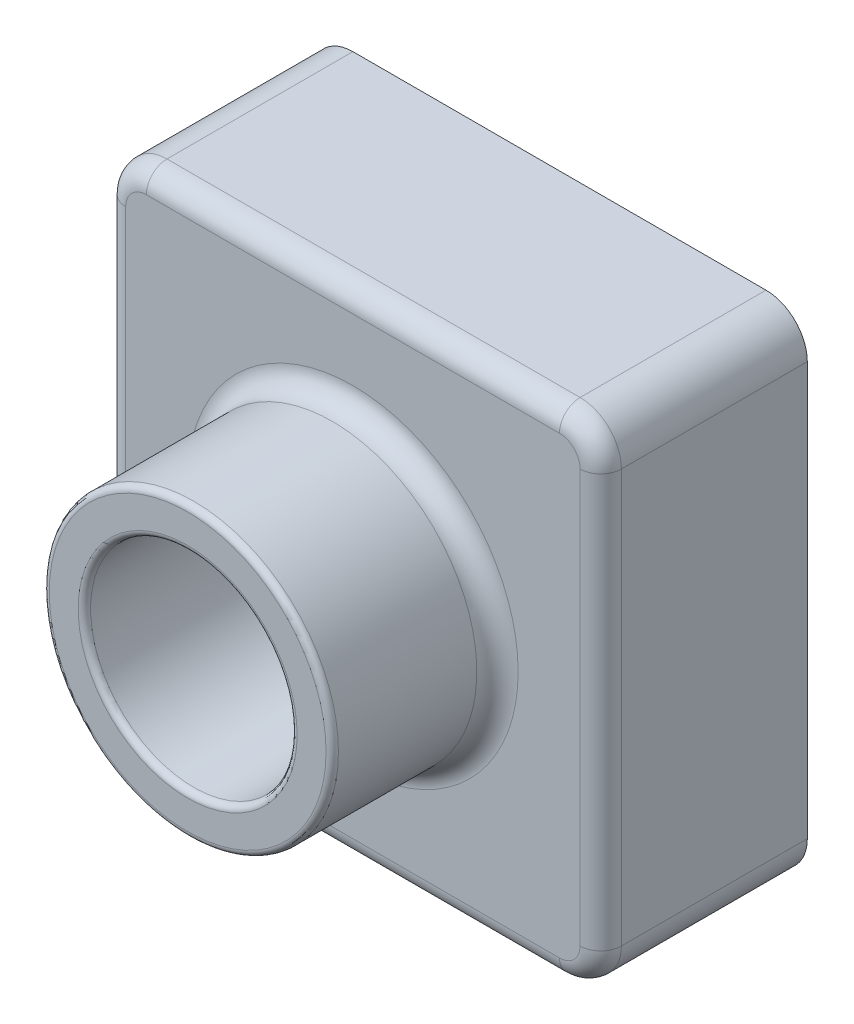
SolidWorks part; units mm, degrees
ref_plane "Front Plane" through (0, 0, 0) normal (0, 0, 1) x (1, 0, 0)
ref_plane "Top Plane" through (0, 0, 0) normal (0, 1, 0) x (1, 0, 0)
ref_plane "Right Plane" through (0, 0, 0) normal (1, 0, 0) x (0, 0, -1)
sketch "Sketch4" plane through (0, 0, 0) normal (0, 0, 1) x (1, 0, 0)
  line L1 (0, 0) -> (120, 0)
  line L2 (0, 0) -> (0, 120)
  line L3 (0, 120) -> (120, 120)
  line L4 (120, 0) -> (120, 120)
  dimension "D1" = 120
  dimension "D2" = 120
extrude "Boss-Extrude3" add sketch "Sketch4" along normal blind 50
sketch "Sketch5" plane through (0, 0, 50) normal (0, 0, 1) x (1, 0, 0)
  circle A0 centre (60, 60) radius 35
extrude "Boss-Extrude4" add sketch "Sketch5" along normal blind 40
sketch "Sketch6" plane through (0, 0, 90) normal (0, 0, 1) x (1, 0, 0)
  circle A0 centre (60, 60) radius 25
extrude "Cut-Extrude1" cut sketch "Sketch6" against normal through all
fillet "Fillet1" radius 10 4 edges at (120, 0, 25) (0, 0, 25) (0, 120, 25) (120, 120, 25)
fillet "Fillet2" radius 1.5 2 edges at (95, 60, 90) (85, 60, 90)
fillet "Fillet3" radius 5 9 edges at (2.9289, 2.9289, 50) (0, 60, 50) (2.9289, 117.0711, 50) (60, 120, 50) (117.0711, 117.0711, 50) (120, 60, 50) (117.0711, 2.9289, 50) (60, 0, 50) (95, 60, 50)
shell "Shell1" thickness 2 removed face at (85, 60, 0)
